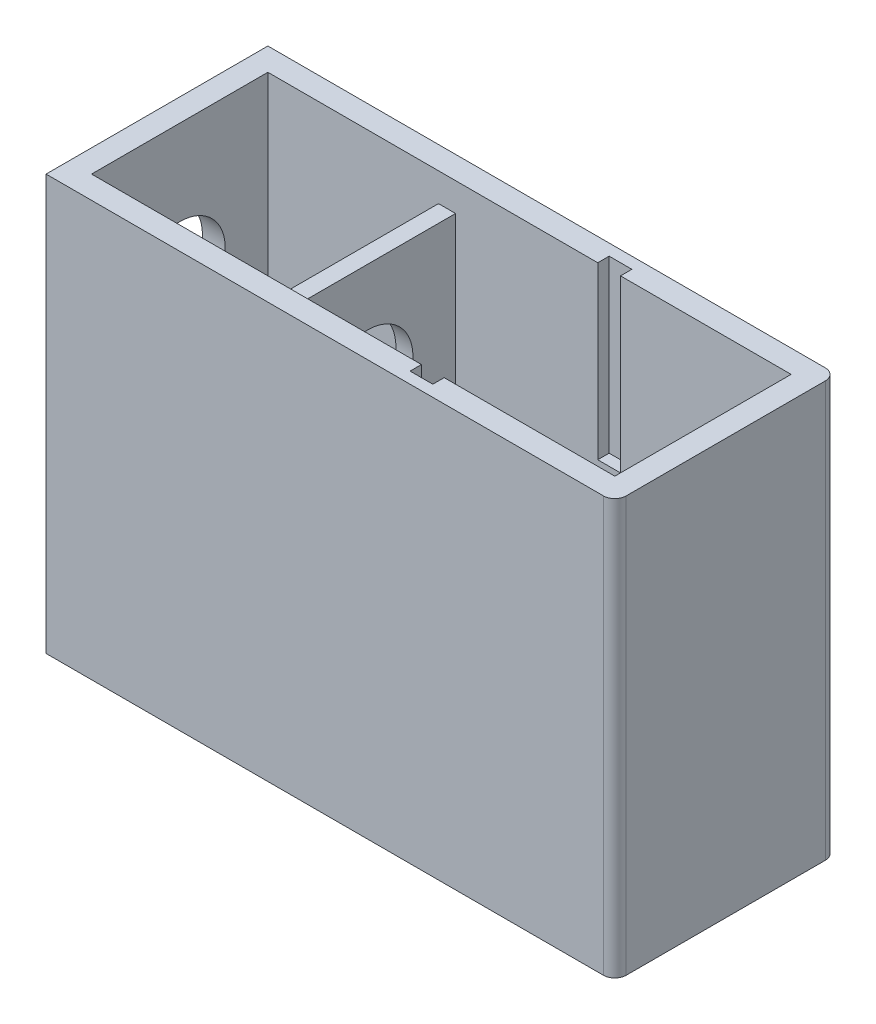
SolidWorks part; units mm, degrees
ref_plane "Front Plane" through (0, 0, 0) normal (0, 0, 1) x (1, 0, 0)
ref_plane "Top Plane" through (0, 0, 0) normal (0, 1, 0) x (1, 0, 0)
ref_plane "Right Plane" through (0, 0, 0) normal (1, 0, 0) x (0, 0, -1)
sketch "Sketch1" plane through (0, 0, 0) normal (0, 1, 0) x (1, 0, 0)
  line L0 (-46, 15.5) -> (-46, -15.5)
  line L1 (-50, 19.5) -> (50, 19.5)
  line L2 (-50, 19.5) -> (-50, -19.5)
  line L3 (-50, -19.5) -> (50, -19.5)
  line L4 (50, 19.5) -> (50, -19.5)
  line L5 (-50, 19.5) -> (50, -19.5) construction
  line L6 (-50, -19.5) -> (50, 19.5) construction
  line L7 (-46, -15.5) -> (46, -15.5)
  line L8 (46, 15.5) -> (46, -15.5)
  line L9 (-46, 15.5) -> (46, 15.5)
  point P0 (0, 0)
  dimension "D1" = 39
  dimension "D2" = 100
  dimension "D3" = 4
extrude "Boss-Extrude2" add sketch "Sketch1" along normal blind 3 contours L9 L0 L7 L8 region at (0, 0, 0)
extrude "Boss-Extrude3" add sketch "Sketch1<3>" along normal blind 73
sketch "Sketch1<3>" plane through (0, 0, 0) normal (0, 1, 0) x (1, 0, 0) same geometry as "Sketch1"
fillet "Fillet1" radius 2 1 edges at (50, 36.5, 19.5)
fillet "Fillet2" radius 2 1 edges at (50, 36.5, -19.5)
sketch "Sketch3" plane through (0, 3, 0) normal (0, 1, 0) x (1, 0, 0)
  line L0 (-46, 15.5) -> (46, 15.5) construction
  line L1 (46, -15.5) -> (38.86, -15.5)
  line L2 (46, -15.5) -> (46, 15.5)
  line L3 (46, 15.5) -> (38.86, 15.5)
  line L4 (38.86, -15.5) -> (38.86, 15.5)
  dimension "D1" = 7.14
extrude "Boss-Extrude4" add sketch "Sketch3" along normal blind 28
sketch "Sketch4" plane through (0, 31, 0) normal (0, 1, 0) x (1, 0, 0)
  line L0 (38.86, -7.08) -> (38.86, -9.931)
  line L1 (38.86, -7.08) -> (46, -7.08)
  line L2 (46, -15.5) -> (46, 15.5) construction
  line L3 (38.86, 15.5) -> (38.86, -15.5) construction
  line L4 (38.86, -9.931) -> (46, -9.931)
  line L5 (46, -9.931) -> (46, -7.08)
  circle A0 centre (43.36, 8.92) radius 0.5
  circle A1 centre (43.36, -1.08) radius 0.5
  line M9 (46, -15.5) -> (46, 15.5)
  line M11 (38.86, 15.5) -> (38.86, -15.5)
extrude "Boss-Extrude5" add sketch "Sketch4" along normal blind 4 contours L4 L1 M11 M9 region at (42.43, 31, 8.5055)
sketch "Sketch5" plane through (0, 31, 0) normal (0, 1, 0) x (1, 0, 0)
  line L4 (46, -15.5) -> (46, -9.931)
  line L5 (46, -9.931) -> (38.86, -9.931)
  line L6 (38.86, -9.931) -> (38.86, -15.5)
  line L7 (38.86, -15.5) -> (46, -15.5)
  line L8 (46, -15.5) -> (46, -9.931)
  line L9 (46, -9.931) -> (38.86, -9.931)
  line L10 (38.86, -9.931) -> (38.86, -15.5)
  line L11 (38.86, -15.5) -> (46, -15.5)
  dimension "D1" = 0
extrude "Cut-Extrude1" cut sketch "Sketch5" against normal blind 28
extrude "Cut-Extrude3" cut sketch "Sketch4<3>" against normal blind 20 contours A1 | A0
sketch "Sketch4<3>" plane through (0, 31, 0) normal (0, 1, 0) x (1, 0, 0) same geometry as "Sketch4"
pattern_linear "LPattern5" count 2 spacing 47.64 along (-1, 0, 0) of "Boss-Extrude4", "Boss-Extrude5", "Cut-Extrude1"
pattern_linear "LPattern6" count 2 spacing 49 along (-1, 0, 0) of "Cut-Extrude3"
sketch "Sketch10" plane through (38.86, 0, 0) normal (-1, 0, 0) x (0, 0, 1)
  line L1 (7.08, 35) -> (9.931, 35)
  line L2 (7.08, 35) -> (7.08, 3)
  line L3 (7.08, 3) -> (9.931, 3)
  line L4 (9.931, 35) -> (9.931, 3)
extrude "Boss-Extrude6" add sketch "Sketch10" along normal blind 41
sketch "Sketch12" plane through (-46, 0, 0) normal (1, 0, 0) x (0, 0, -1)
  line L1 (15.5, 73) -> (15.5, 3) construction
  line L2 (15.5, 50) -> (-15.5, 50)
  line L3 (-15.5, 73) -> (-15.5, 3) construction
  circle A0 centre (0, 50) radius 8
extrude "Cut-Extrude4" cut sketch "Sketch12" along normal blind 36 and the other way blind 35 contours L2 A0 | L2 A0 region at (-46, 46.6047, 0) region at (-46, 53.3953, 0)
sketch "Sketch13" plane through (0, 3, 0) normal (0, 1, 0) x (1, 0, 0)
  line L0 (46, 15.5) -> (-46, 15.5) construction
  line L1 (-16, 15.5) -> (-13, 15.5)
  line L2 (-16, 15.5) -> (-16, -15.5)
  line L3 (-16, -15.5) -> (-13, -15.5)
  line L4 (-13, 15.5) -> (-13, -15.5)
  line L5 (-46, -15.5) -> (46, -15.5) construction
  dimension "D1" = 3
extrude "Boss-Extrude7" add sketch "Sketch13" along normal blind 65
sketch "Sketch14" plane through (-16, 0, 0) normal (-1, 0, 0) x (0, 0, 1)
  circle A0 centre (0, 50) radius 8
extrude "Cut-Extrude5" cut sketch "Sketch14" against normal blind 5
sketch "Sketch15" plane through (0, 73, 0) normal (0, 1, 0) x (1, 0, 0)
  line L0 (46, 15.5) -> (-46, 15.5) construction
  line L1 (12, 15.5) -> (16, 15.5)
  line L2 (12, 15.5) -> (12, 17.5)
  line L3 (12, 17.5) -> (16, 17.5)
  line L4 (16, 15.5) -> (16, 17.5)
  line L5 (-13, -15.5) -> (-13, 15.5) construction
  line L8 (-13, -15.5) -> (46, -15.5) construction
  line L9 (12, -15.5) -> (16, -15.5)
  line L10 (12, -15.5) -> (12, -17.5)
  line L11 (12, -17.5) -> (16, -17.5)
  line L12 (16, -15.5) -> (16, -17.5)
  dimension "D1" = 4
  dimension "D2" = 2
  dimension "D3" = 25
  dimension "D4" = 2
  dimension "D5" = 4
extrude "Cut-Extrude6" cut sketch "Sketch15" against normal blind 30
